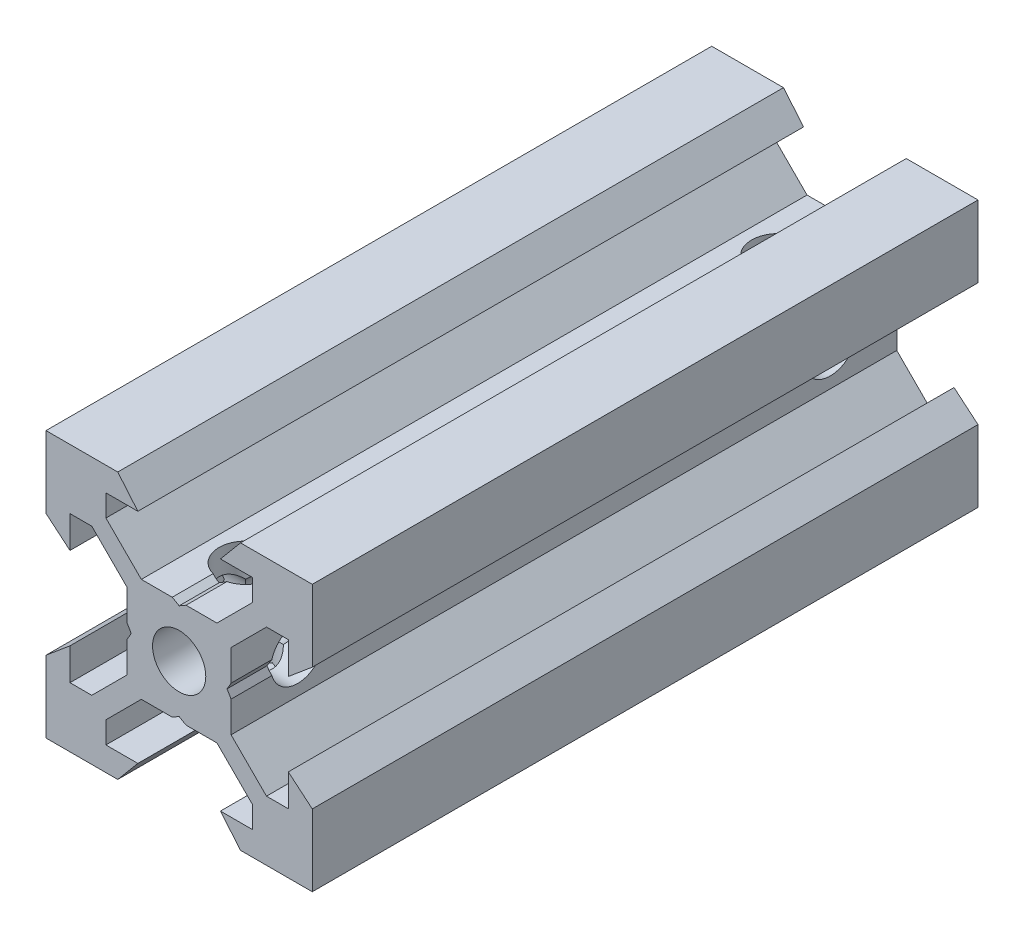
SolidWorks part; units mm, degrees
material "3.3535 (EN-AW 5754)"
ref_plane "Front Plane" through (0, 0, 0) normal (0, 0, 1) x (1, 0, 0)
ref_plane "Top Plane" through (0, 0, 0) normal (0, 1, 0) x (1, 0, 0)
ref_plane "Right Plane" through (0, 0, 0) normal (1, 0, 0) x (0, 0, -1)
sketch "Sketch1" plane through (0, 0, 0) normal (0, 0, 1) x (1, 0, 0)
  line L0 (10, 10) -> (4.6104, 10) construction
  line L1 (10, 10) -> (10, 4.6104) construction
  line L2 (10, -10) -> (10, -4.6104) construction
  line L3 (10, -10) -> (4.6104, -10) construction
  line L4 (10, 10) -> (10, 4.6104)
  line L5 (6.5607, 5.5) -> (8.2, 5.5)
  line L6 (5.5, 8.2) -> (5.5, 6.5607)
  line L7 (10, 10) -> (4.6104, 10)
  line L8 (10, 10) -> (10, 4.6104)
  line L9 (6.5607, 5.5) -> (3.9, 2.8393)
  line L10 (5.5, 6.5607) -> (2.8393, 3.9)
  line L11 (10, 4.6104) -> (8.2, 3.1)
  line L12 (4.6104, 10) -> (3.1, 8.2)
  line L13 (8.2, 3.1) -> (8.2, 5.5)
  line L14 (3.1, 8.2) -> (5.5, 8.2)
  line L15 (-6.5607, 5.5) -> (-8.2, 5.5)
  line L16 (6.5607, -5.5) -> (8.2, -5.5)
  line L17 (3.1, -8.2) -> (5.5, -8.2)
  line L18 (8.2, -3.1) -> (8.2, -5.5)
  line L19 (4.6104, -10) -> (3.1, -8.2)
  line L20 (10, -4.6104) -> (8.2, -3.1)
  line L21 (0.5196, -3.9) -> (0, -3.6)
  line L22 (0.5196, 3.9) -> (0, 3.6)
  line L23 (3.6, 0) -> (3.9, -0.5196)
  line L24 (3.9, 0.5196) -> (3.6, 0)
  line L25 (3.9, 0.5196) -> (3.9, 2.8393)
  line L26 (2.8393, 3.9) -> (0.5196, 3.9)
  line L27 (3.9, -2.8393) -> (3.9, -0.5196)
  line L28 (2.8393, -3.9) -> (0.5196, -3.9)
  line L29 (5.5, -6.5607) -> (2.8393, -3.9)
  line L30 (6.5607, -5.5) -> (3.9, -2.8393)
  line L31 (10, -10) -> (10, -4.6104)
  line L32 (10, -10) -> (4.6104, -10)
  line L33 (5.5, -8.2) -> (5.5, -6.5607)
  line L34 (-6.5607, -5.5) -> (-8.2, -5.5)
  line L35 (10, -10) -> (10, -4.6104)
  line L36 (0, 0) -> (0, 8.2) construction
  line L37 (-10, -10) -> (-4.6104, -10) construction
  line L38 (-10, -10) -> (-10, -4.6104) construction
  line L39 (-10, 10) -> (-10, 4.6104) construction
  line L40 (-10, 10) -> (-4.6104, 10) construction
  line L41 (-10, -10) -> (-10, -4.6104)
  line L43 (-5.5, -8.2) -> (-5.5, -6.5607)
  line L44 (-10, -10) -> (-4.6104, -10)
  line L45 (-10, -10) -> (-10, -4.6104)
  line L46 (-6.5607, -5.5) -> (-3.9, -2.8393)
  line L47 (-5.5, -6.5607) -> (-2.8393, -3.9)
  line L48 (-2.8393, -3.9) -> (-0.5196, -3.9)
  line L49 (-3.9, -2.8393) -> (-3.9, -0.5196)
  line L50 (-2.8393, 3.9) -> (-0.5196, 3.9)
  line L51 (-3.9, 0.5196) -> (-3.9, 2.8393)
  line L52 (-3.9, 0.5196) -> (-3.6, 0)
  line L53 (-3.6, 0) -> (-3.9, -0.5196)
  line L54 (-0.5196, 3.9) -> (0, 3.6)
  line L55 (-0.5196, -3.9) -> (0, -3.6)
  line L56 (-10, -4.6104) -> (-8.2, -3.1)
  line L57 (-4.6104, -10) -> (-3.1, -8.2)
  line L58 (-8.2, -3.1) -> (-8.2, -5.5)
  line L59 (-3.1, -8.2) -> (-5.5, -8.2)
  line L60 (-10, -10) -> (10, -10) construction
  line L61 (-10, -10) -> (-10, 10) construction
  line L62 (-3.1, 8.2) -> (-5.5, 8.2)
  line L63 (-8.2, 3.1) -> (-8.2, 5.5)
  line L64 (-4.6104, 10) -> (-3.1, 8.2)
  line L65 (-10, 4.6104) -> (-8.2, 3.1)
  line L66 (-5.5, 6.5607) -> (-2.8393, 3.9)
  line L67 (-6.5607, 5.5) -> (-3.9, 2.8393)
  line L68 (-10, 10) -> (-10, 4.6104)
  line L69 (-10, 10) -> (-4.6104, 10)
  line L70 (-5.5, 8.2) -> (-5.5, 6.5607)
  line L71 (-10, 10) -> (10, 10) construction
  line L72 (-10, 10) -> (-10, 4.6104)
  line L73 (10, -10) -> (10, 10) construction
  line L74 (-10, -10) -> (10, 10) construction
  line L75 (-10, 10) -> (10, -10) construction
  circle A0 centre (0, 0) radius 2
  dimension "D7" = 4
  dimension "D1" = 20
  dimension "D2" = 5.3896
  dimension "D3" = 4.5
  dimension "D4" = 50
  dimension "D5" = 1.8
  dimension "D6" = 1.5104
  dimension "D8" = 5.5
  dimension "D9" = 120
  dimension "D10" = 0.3
  dimension "D11" = 2.3197
  dimension "D12" = 7.8
  dimension "D13" = 7.8
  dimension "D14" = 1.5
  dimension "D15" = 2.6607
extrude "Boss-Extrude1" add sketch "Sketch1" along normal blind 50 contours L70 L62 L64 L69 L68 L65 L63 L15 L67 L51 L52 L53 L49 L46 L34 L58 L56 L41 L44 L57 L59 L43 L47 L48 L55 L21 L28 L29 L33 L17 L19 L32 L31 L20 L18 L16 L30 L27 L23 L24 L25 L9 L5 L13 L11 L4 L7 L12 L14 L6 L10 region at (9.7172, 7.3052, 0)
sketch "Sketch2" plane through (0, -3.9, 0) normal (0, -1, 0) x (-1, 0, 0)
  line L0 (0, -50) -> (0, -5) construction
  line L1 (0, -50) -> (0, 0) construction
  line L2 (0, 0) -> (0, -45) construction
  circle A0 centre (0, -5) radius 2
  circle A1 centre (0, -45) radius 2
  dimension "D2" = 4
  dimension "D4" = 4
  dimension "D1" = 45
  dimension "D3" = 45
extrude "Cut-Extrude1" cut sketch "Sketch2" against normal through all both and the other way through all
sketch "Sketch3" plane through (3.9, 0, 0) normal (1, 0, 0) x (0, 0, -1)
  line L0 (0, 0) -> (-45, 0) construction
  line L1 (-50, 0) -> (0, 0) construction
  line L2 (-50, 0) -> (-5, 0) construction
  circle A0 centre (-45, 0) radius 2
  circle A1 centre (-5, 0) radius 2
  dimension "D2" = 4
  dimension "D4" = 4
  dimension "D1" = 45
  dimension "D3" = 45
extrude "Cut-Extrude2" cut sketch "Sketch3" against normal through all both
